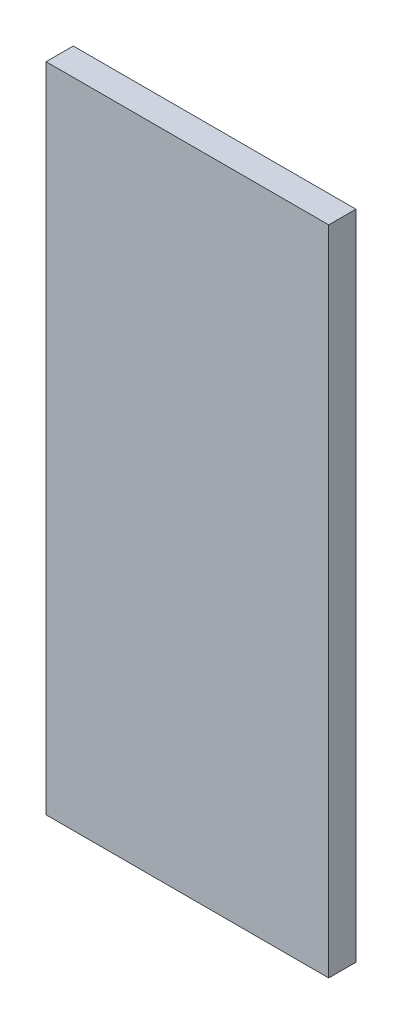
SolidWorks part; units mm, degrees
ref_plane "Front Plane" through (0, 0, 0) normal (0, 0, 1) x (1, 0, 0)
ref_plane "Top Plane" through (0, 0, 0) normal (0, 1, 0) x (1, 0, 0)
ref_plane "Right Plane" through (0, 0, 0) normal (1, 0, 0) x (0, 0, -1)
sketch "Sketch1" plane through (0, 0, 0) normal (0, 0, 1) x (1, 0, 0)
  line L0 (-1.6554, -40.741) -> (-1.6554, 111.659) construction
  line L1 (-34.6754, -40.741) -> (31.3646, -40.741)
  line L2 (-34.6754, -40.741) -> (-34.6754, 111.659)
  line L3 (-34.6754, 111.659) -> (31.3646, 111.659)
  line L4 (31.3646, -40.741) -> (31.3646, 111.659)
  line L5 (-34.6754, -40.741) -> (-34.6754, 111.659) construction
  line L6 (31.3646, 111.659) -> (31.3646, -40.741) construction
  dimension "D2" = 152.4
extrude "Boss-Extrude1" add sketch "Sketch1" along normal blind 6.35
